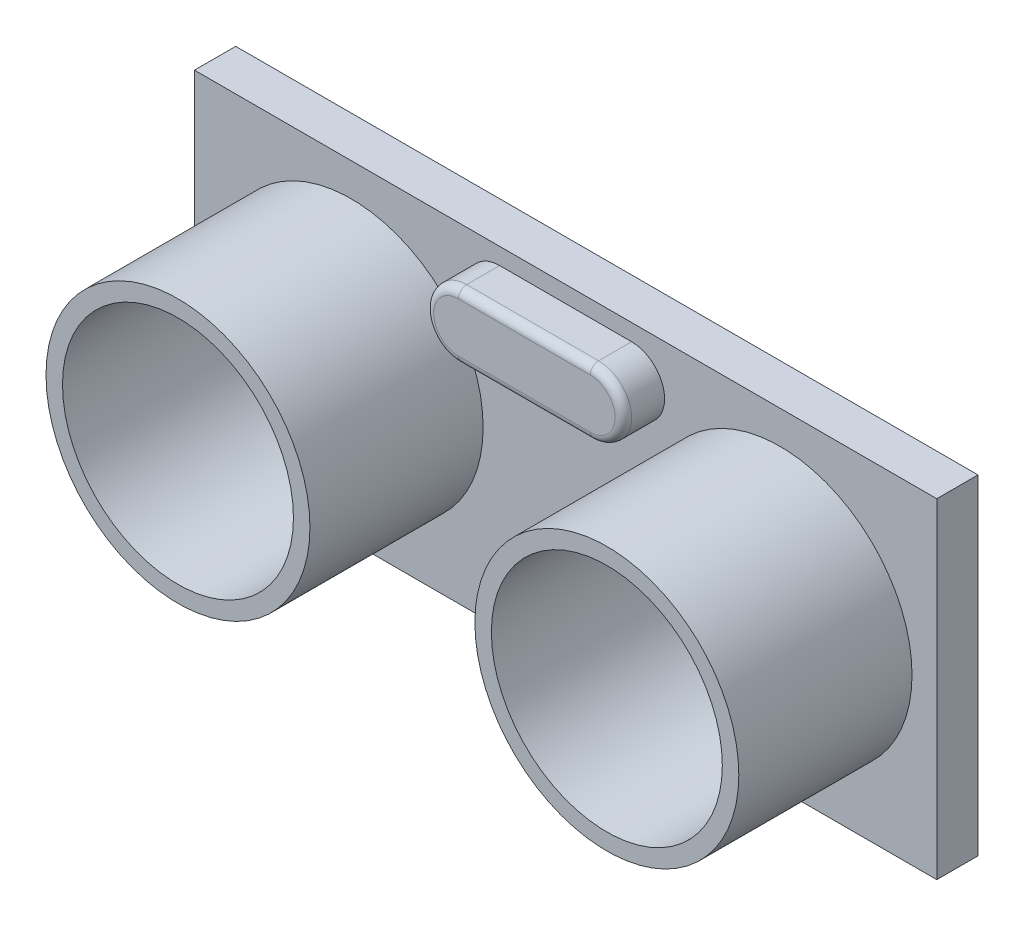
SolidWorks part; units mm, degrees
ref_plane "Front Plane" through (0, 0, 0) normal (0, 0, 1) x (1, 0, 0)
ref_plane "Top Plane" through (0, 0, 0) normal (0, 1, 0) x (1, 0, 0)
ref_plane "Right Plane" through (0, 0, 0) normal (1, 0, 0) x (0, 0, -1)
sketch "Sketch1" plane through (0, 0, 0) normal (0, 0, 1) x (1, 0, 0)
  line L0 (0, 0) -> (0, 14.174) construction
  line L1 (-22.5, -10) -> (22.5, -10)
  line L2 (-22.5, -10) -> (-22.5, 10)
  line L3 (-22.5, 10) -> (22.5, 10)
  line L4 (22.5, -10) -> (22.5, 10)
  line L5 (-22.5, -10) -> (22.5, 10) construction
  line L6 (-22.5, 10) -> (22.5, -10) construction
  line L7 (-4, 6.9918) -> (4, 6.9918) construction
  line L8 (-4, 8.9918) -> (4, 8.9918)
  line L9 (-4, 4.9918) -> (4, 4.9918)
  circle A0 centre (13, 0) radius 8
  circle A1 centre (-13, 0) radius 8
  circle A2 centre (13, 0) radius 7
  circle A3 centre (-13, 0) radius 7
  arc A4 (-4, 8.9918) -> (-4, 4.9918) centre (-4, 6.9918) ccw
  arc A5 (4, 4.9918) -> (4, 8.9918) centre (4, 6.9918) ccw
  point P0 (0, 0)
  point P18 (0, 6.9918)
  dimension "D3" = 13
  dimension "D7" = 2
  dimension "D1" = 45
  dimension "D2" = 20
  dimension "D6" = 8
  dimension "D4" = 1
  dimension "D5" = 1
extrude "Boss-Extrude1" add sketch "Sketch1" along normal blind 12 contours A1 A3 | A0 A2 region at (5.2263, 0, 0) region at (-20.7737, 0, 0)
extrude "Boss-Extrude2" add sketch "Sketch1<4>" along normal blind 1.5 contours L1 L4 L3 L2 A5 L9 A4 L8 A0 A1 region at (0, -0.6874, 0)
sketch "Sketch1<4>" plane through (0, 0, 0) normal (0, 0, 1) x (1, 0, 0) same geometry as "Sketch1"
extrude "Boss-Extrude3" add sketch "Sketch1<5>" along normal blind 4 contours L9 A5 L8 A4 region at (0, 6.9918, 0)
sketch "Sketch1<5>" plane through (0, 0, 0) normal (0, 0, 1) x (1, 0, 0) same geometry as "Sketch1"
fillet "Fillet1" radius 0.5 4 edges at (-6, 6.9918, 4) (0, 4.9918, 4) (6, 6.9918, 4) (0, 8.9918, 4)
sketch "Sketch2" plane through (0, 0, 0) normal (0, 0, -1) x (-1, 0, 0)
  line L0 (-22.5, -10) -> (-22.5, 10) construction
  line L1 (3, -6.0566) -> (4, -6.0566)
  line L2 (2.5, -6.5566) -> (2.5, -7.5566)
  line L3 (3, -8.0566) -> (4, -8.0566)
  line L4 (4.5, -6.5566) -> (4.5, -7.5566)
  arc A0 (2.5, -7.5566) -> (3, -8.0566) centre (3, -7.5566) ccw
  arc A1 (4, -8.0566) -> (4.5, -7.5566) centre (4, -7.5566) ccw
  arc A2 (4, -6.0566) -> (4.5, -6.5566) centre (4, -6.5566) cw
  arc A3 (3, -6.0566) -> (2.5, -6.5566) centre (3, -6.5566) ccw
  point P6 (2.5, -8.0566)
  point P11 (4.5, -6.0566)
  point P14 (2.5, -6.0566)
  dimension "D3" = 0.5
  dimension "D1" = 2
  dimension "D2" = 2
  dimension "D4" = 25
extrude "Boss-Extrude5" add sketch "Sketch2" along normal blind 2
pattern_linear "LPattern1" count 4 spacing 2 along (1, 0, 0) of "Boss-Extrude5"
ref_plane "Plane5" through (2.5, 0, 0) normal (1, 0, 0) x (0, 0, -1)
sketch "Sketch9" plane through (2.5, 0, 0) normal (1, 0, 0) x (0, 0, -1)
  line L0 (2, -7.0566) -> (2.1, -7.0566)
  line L1 (2.5, -7.4566) -> (2.5, -13.0566)
  line L2 (2, -6.5566) -> (2, -7.5566) construction
  arc A0 (2.1, -7.0566) -> (2.5, -7.4566) centre (2.1, -7.4566) cw
  point P7 (2.5, -7.0566)
  dimension "D4" = 0.4
  dimension "D1" = 0.5
  dimension "D2" = 6
  dimension "D3" = 0
sketch "Sketch10" plane through (0, 0, -2) normal (0, 0, -1) x (-1, 0, 0)
  circle A0 centre (-2.5, -7.0566) radius 0.2
sweep "Sweep1" add profiles "Sketch10" path "Sketch9"
pattern_linear "LPattern2" count 4 spacing 2 along (-1, 0, 0) of "Sweep1"
sketch "Sketch11" plane through (0, 0, 0) normal (0, 0, -1) x (-1, 0, 0)
  line L0 (22.5, -10) -> (22.5, 10) construction
  line L1 (-22.5, 10) -> (22.5, 10)
  line L2 (-22.5, 10) -> (-22.5, -10)
  line L3 (-22.5, -10) -> (22.5, -10)
  line L4 (22.5, 10) -> (22.5, -10)
extrude "Boss-Extrude6" add sketch "Sketch11" along normal blind 1
